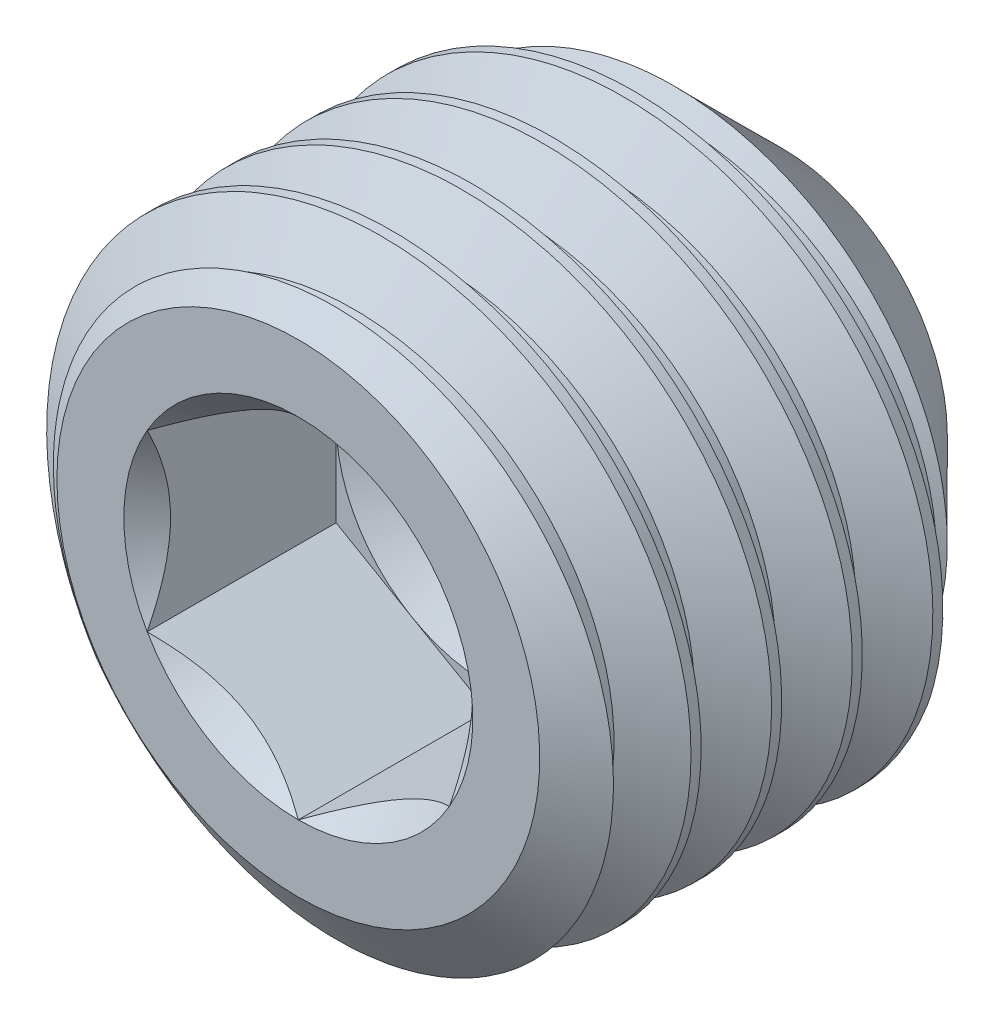
SolidWorks part; units mm, degrees
ref_plane "Front" through (0, 0, 0) normal (0, 0, 1) x (1, 0, 0)
ref_plane "Top" through (0, 0, 0) normal (0, 1, 0) x (1, 0, 0)
ref_plane "Right" through (0, 0, 0) normal (1, 0, 0) x (0, 0, -1)
sketch "Sketch22" plane through (0, 0, 0) normal (1, 0, 0) x (0, 0, -1)
  line L0 (-2.5227, 0) -> (-2.5227, 3.1699)
  line L1 (-2.5227, 3.1699) -> (-1.9678, 3.9624)
  line L2 (-1.9678, 3.9624) -> (2.0362, 3.9624)
  line L3 (2.0362, 3.9624) -> (3.8273, 2.1713)
  line L4 (3.8273, 2.1713) -> (2.5227, 0)
  line L5 (2.5227, 0) -> (-2.5227, 0)
  line L6 (2.5227, 0) -> (3.8273, 0) construction
  line L7 (3.8273, 0) -> (3.8273, 2.1713) construction
  line L8 (3.8273, -2.1713) -> (2.5227, 0) construction
  line L9 (-1.9678, -3.9624) -> (2.0362, -3.9624) construction
  dimension "Dia" = 7.9248
  dimension "Length" = 6.35
  dimension "D3" = 35
  dimension "D5" = 118
  dimension "D6" = 45
  dimension "D7" = 6.3398
revolve "Revolve1" add sketch "Sketch22" angle 360 about L6
ref_plane "Plane1" through (0, 0, -3.8273) normal (0, 0, 1) x (1, 0, 0)
sketch "Sketch27" plane through (0, 0, -3.8273) normal (0, 0, 1) x (1, 0, 0)
  circle A0 centre (0, 0) radius 3.9624 construction
  circle A1 centre (0, 0) radius 3.9624
curve "Helix/Spiral1" pitch 1.0583 height 8.7393 radius 3.9624 centre (0, 0, -3.8273) axis (0, 0, 1) start towards (1, 0, 0)
sketch "Sketch28" plane through (0, 0, 0) normal (1, 0, 0) x (0, 0, -1)
  line L0 (3.8273, 3.9624) -> (4.7534, 3.9624)
  line L1 (4.7534, 3.9624) -> (4.3829, 3.3208)
  line L2 (4.3829, 3.3208) -> (4.1977, 3.3208)
  line L3 (4.1977, 3.3208) -> (3.8273, 3.9624)
  line L4 (4.0125, 3.6416) -> (4.5681, 3.6416) construction
  line L6 (-1.9678, 3.9624) -> (2.0362, 3.9624) construction
  line L7 (3.8273, 4.3641) -> (3.8273, -4.3641) construction
  dimension "D1" = 0.1852
  dimension "D3" = 60
  dimension "D2" = 0.926
sweep "Cut-Sweep2" cut profiles "Sketch28" path "Helix/Spiral1" align with end faces yes
sketch "Sketch23" plane through (0, 0, 2.5227) normal (0, 0, 1) x (1, 0, 0)
  line L1 (0, 2.2914) -> (-1.9844, 1.1457)
  line L2 (-1.9844, 1.1457) -> (-1.9844, -1.1457)
  line L3 (-1.9844, -1.1457) -> (0, -2.2914)
  line L4 (0, -2.2914) -> (1.9844, -1.1457)
  line L5 (1.9844, -1.1457) -> (1.9844, 1.1457)
  line L6 (1.9844, 1.1457) -> (0, 2.2914)
  circle A0 centre (0, 0) radius 1.9844 construction
  dimension "Hex" = 3.9688
extrude "Cut-Extrude10" cut sketch "Sketch23" against normal blind 2.4805
sketch "Sketch24" plane through (0, 0, 2.5227) normal (0, 0, 1) x (1, 0, 0)
  circle A0 centre (0, 0) radius 2.2914
extrude "Cut-Extrude11" cut sketch "Sketch24" against normal through all draft 45
sketch "Sketch26" plane through (0, 0, 0.0422) normal (0, 0, 1) x (1, 0, 0)
  circle A0 centre (0, 0) radius 1.9844 construction
  circle A1 centre (0, 0) radius 1.9844
extrude "Cut-Extrude12" cut sketch "Sketch26" against normal through all draft 60
sketch "Sketch30" plane through (0, 0, 0) normal (1, 0, 0) x (0, 0, -1)
  line L0 (-1.9678, 3.9624) -> (2.0362, 3.9624) construction
  line L1 (-2.5227, 0) -> (-2.5227, 3.1699) construction
  line L2 (3.8273, 0) -> (3.8273, 2.1713) construction
  line L3 (-1.9678, -3.9624) -> (2.0362, -3.9624) construction
  point P0 (-2.5227, 3.9624)
  point P1 (3.8273, 3.9624)
  point P2 (3.8273, -3.9624)
  point P11 (1.1815, -3.9624)
  dimension "D1" = 2.6458
sketch "Sketch31" plane through (0, 0, 0) normal (1, 0, 0) x (0, 0, -1)
  line L2 (2.5227, 0) -> (3.8273, -2.1713)
  line L3 (3.8273, 2.1713) -> (2.5227, 0)
equation "\"D7@Sketch22\"=\"Dia@Sketch22\"*.8"
equation "\"D1@Sketch28\" = \"D4@Helix/Spiral1\" * .175"
equation "\"D3@Helix/Spiral1\" = \"Length@Sketch22\" + \"D4@Helix/Spiral1\" + .0524"
equation "\"D1@Sketch30\" = \"D4@Helix/Spiral1\" * 2.5"
equation "\"hex Depth@Cut-Extrude10\" = \"Hex@Sketch23\" * .625"
equation "\"D2@Sketch28\" = \"D4@Helix/Spiral1\" * .875"
